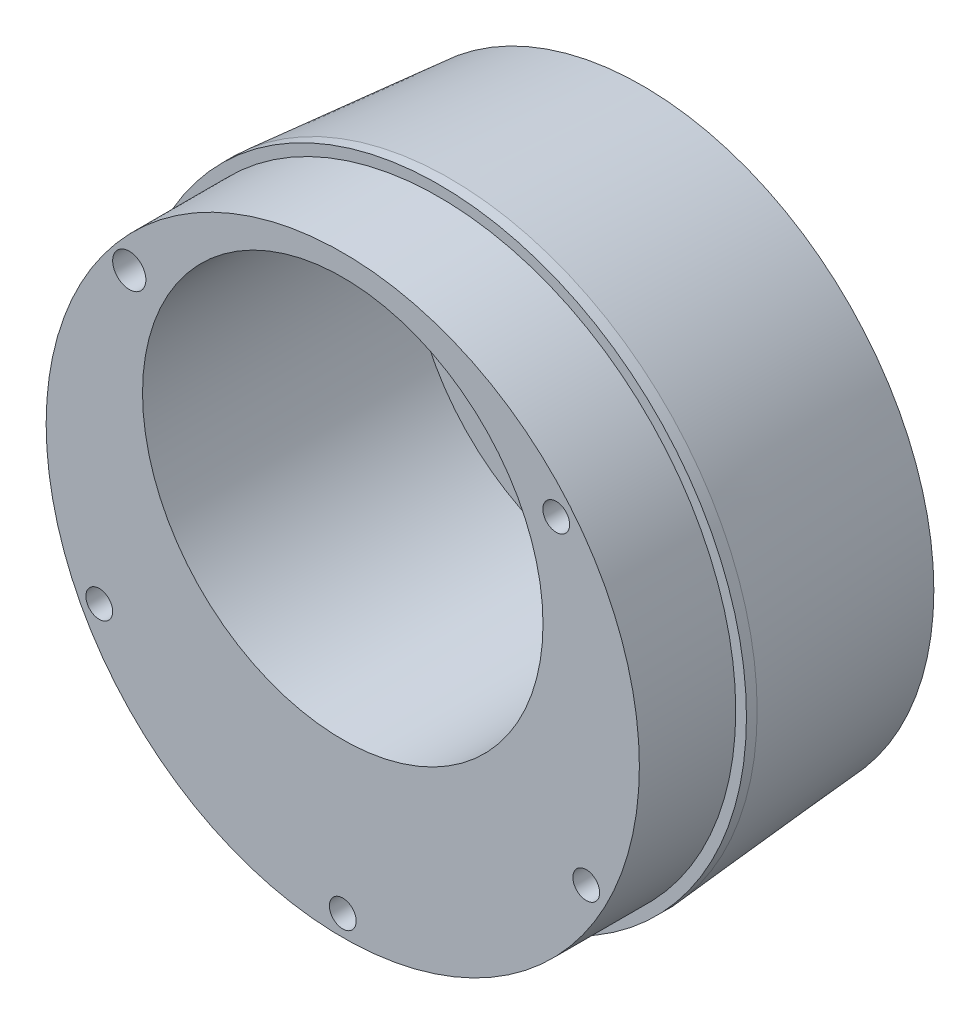
SolidWorks part; units mm, degrees
ref_plane "Спереди" through (0, 0, 0) normal (0, 0, 1) x (1, 0, 0)
ref_plane "Сверху" through (0, 0, 0) normal (0, 1, 0) x (1, 0, 0)
ref_plane "Справа" through (0, 0, 0) normal (1, 0, 0) x (0, 0, -1)
sketch "Sketch1" plane through (0, 0, 0) normal (0, 0, 1) x (1, 0, 0)
  circle A0 centre (0, 0) radius 28.7
  circle A1 centre (0, 0) radius 6.15
  circle A3 centre (0, 7) radius 15.5 construction
  circle A4 centre (15.5, 7) radius 1.65
  circle A5 centre (7.75, -6.4234) radius 1.65
  circle A6 centre (-7.75, -6.4234) radius 1.65
  circle A7 centre (-15.5, 7) radius 1.65
  circle A8 centre (-7.75, 20.4234) radius 1.65
  circle A9 centre (7.75, 20.4234) radius 1.65
  point P20 (0, 7)
  dimension "D1" = 57.4
  dimension "D2" = 12.3
  dimension "D3" = 7
  dimension "D4" = 31
  dimension "D5" = 3.3
  dimension "D6" = 6
extrude "Основа" add sketch "Sketch1" along normal blind 28
sketch "Sketch2" plane through (0, 0, 28) normal (0, 0, 1) x (1, 0, 0)
  circle A0 centre (0, 7) radius 18.7
  dimension "D1" = 37.4
  dimension "D2" = 7
extrude "Посадочное под двигатель" cut sketch "Sketch2" against normal offset from surface (25 mm away) 3 up to face at (28.7, 0, 0)
sketch "Sketch4" plane through (0, 0, 28) normal (0, 0, 1) x (1, 0, 0)
  circle A0 centre (0, 0) radius 27.7
  circle A1 centre (0, 0) radius 28.7
  circle A2 centre (0, 0) radius 28.7 construction
  dimension "D1" = 55.4
extrude "Вырез под внутреннее кольцо подшипника" cut sketch "Sketch4" against normal blind 9
sketch "Sketch5" plane through (0, 0, 28) normal (0, 0, 1) x (1, 0, 0)
  line L0 (0, 7) -> (0, -25.75) construction
  line L1 (-22.74, -12.0811) -> (0, 7) construction
  line L2 (0, 7) -> (-19.9369, 16.2967) construction
  circle A1 centre (0, 7) radius 18.7 construction
  circle A3 centre (-22.74, -12.0811) radius 1.25
  circle A12 centre (0, 0) radius 25.75 construction
  circle A13 centre (0, 7) radius 18.7 construction
  circle A14 centre (0, -25.75) radius 1.25
  circle A15 centre (19.9369, 16.2967) radius 1.25
  circle A16 centre (22.74, -12.0811) radius 1.25
  circle A17 centre (-19.9369, 16.2967) radius 1.55
  dimension "D1" = 51.5
  dimension "D4" = 2.5
  dimension "D5" = 3.1
  dimension "D2" = 50
  dimension "D3" = 115
extrude "Под шурупы крепления шайбы колена" cut sketch "Sketch5" against normal blind 10
sketch "Эскиз1" plane through (0, 0, 0) normal (0, 0, -1) x (-1, 0, 0)
  circle A0 centre (-7.75, 20.4234) radius 3
  circle A1 centre (7.75, 20.4234) radius 3
  circle A2 centre (15.5, 7) radius 3
  circle A3 centre (7.75, -6.4234) radius 3
  circle A4 centre (-7.75, -6.4234) radius 3
  circle A5 centre (-15.5, 7) radius 3
  dimension "D1" = 6
extrude "Углубления под шляпки" cut sketch "Эскиз1" against normal blind 0.5
chamfer "Скругления под шляпки винтов крепления двигателя к стакану" distance 1.5 angle 45 6 edges at (13.85, 7, 0.5) (6.1, -6.4234, 0.5) (-9.4, -6.4234, 0.5) (-17.15, 7, 0.5) (-9.4, 20.4234, 0.5) (6.1, 20.4234, 0.5)
chamfer "Фаска1" distance 1.5 distance2 18 1 edges at (28.7, 0, 0) first distance on face at (12.5, 7, 0)
